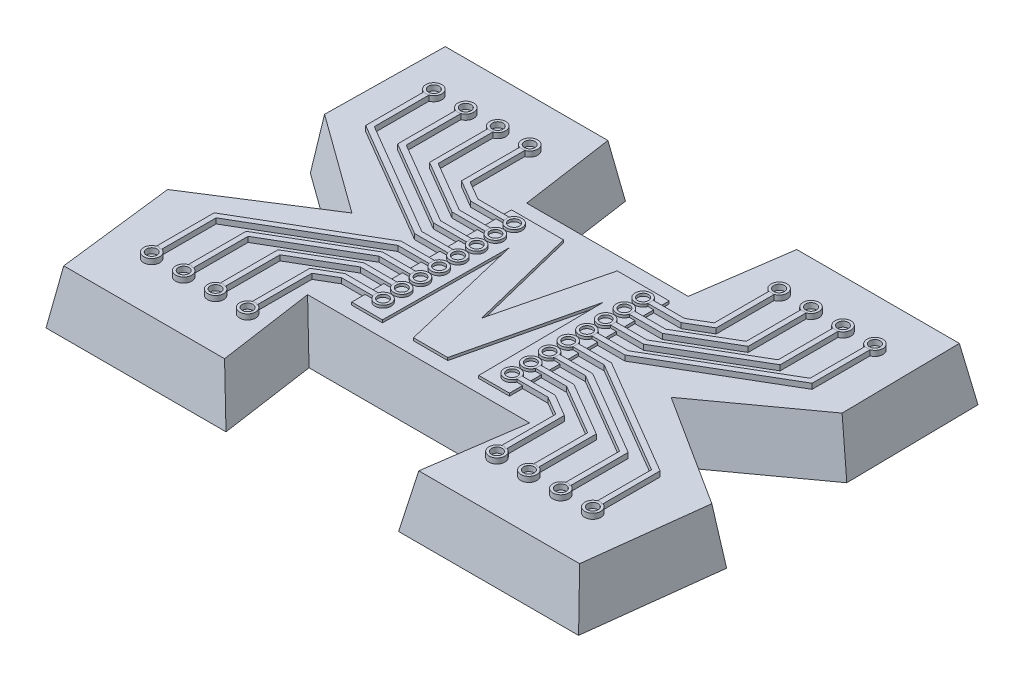
SolidWorks part; units mm, degrees
ref_plane "Спереди" through (0, 0, 0) normal (0, 0, 1) x (1, 0, 0)
ref_plane "Сверху" through (0, 0, 0) normal (0, 1, 0) x (1, 0, 0)
ref_plane "Справа" through (0, 0, 0) normal (1, 0, 0) x (0, 0, -1)
sketch "Эскиз1" plane through (0, 0, 0) normal (0, 1, 0) x (1, 0, 0)
  line L0 (0, 0) -> (-5.9483, 49.6449)
  line L1 (-5.9483, 49.6449) -> (33.7998, 75)
  line L2 (33.7998, 75) -> (-0.7287, 100.0053)
  line L3 (-0.7287, 100.0053) -> (0, 150)
  line L4 (0, 150) -> (67.5996, 150)
  line L5 (67.5996, 150) -> (72.7258, 114.3707)
  line L6 (72.7258, 114.3707) -> (127.2742, 114.3707)
  line L7 (0, 0) -> (67.5996, 0)
  line L8 (67.5996, 0) -> (62.3599, 36.418)
  line L9 (62.3599, 36.418) -> (137.6401, 36.418)
  line L10 (100, 114.3707) -> (100, 36.418) construction
  line L11 (33.7998, 0) -> (33.7998, 150) construction
  line L12 (166.2002, 0) -> (166.2002, 150) construction
  line L13 (132.4004, 0) -> (137.6401, 36.418)
  line L14 (200, 0) -> (132.4004, 0)
  line L15 (132.4004, 150) -> (127.2742, 114.3707)
  line L16 (200, 150) -> (132.4004, 150)
  line L17 (200.7287, 100.0053) -> (200, 150)
  line L18 (166.2002, 75) -> (200.7287, 100.0053)
  line L19 (205.9483, 49.6449) -> (166.2002, 75)
  line L20 (200, 0) -> (205.9483, 49.6449)
  dimension "D1" = 100
  dimension "D3" = 150
  dimension "D4" = 50
extrude "X" add sketch "Эскиз1" along normal blind 20 draft 10
sketch "Эскиз6" plane through (0, 20, 0) normal (0, 1, 0) x (1, 0, 0)
  line L0 (70, 104.8152) -> (70, 44.8152)
  line L1 (99.6154, 63.8897) -> (99.6154, 44.8152) construction
  line L2 (70, 44.8152) -> (81.5385, 44.8152)
  line L3 (81.5385, 44.8152) -> (81.9231, 92.0507)
  line L4 (81.9231, 92.0507) -> (93.1851, 44.8152)
  line L5 (70, 123.5265) -> (124.007, 123.5265) construction
  line L6 (93.1851, 44.8152) -> (106.0457, 44.8152)
  line L7 (106.0457, 44.8152) -> (117.3077, 92.0507)
  line L8 (117.3077, 92.0507) -> (117.6923, 44.8152)
  line L9 (117.6923, 44.8152) -> (129.2308, 44.8152)
  line L10 (129.2308, 44.8152) -> (129.2308, 104.8152)
  line L11 (70, 123.5265) -> (70, 26.4735) construction
  line L12 (70, 26.4735) -> (124.007, 26.4735) construction
  line L13 (129.2308, 104.8152) -> (109.7115, 104.8152)
  line L14 (109.7115, 104.8152) -> (99.6154, 63.8897)
  line L15 (99.6154, 63.8897) -> (89.5192, 104.8152)
  line L16 (89.5192, 104.8152) -> (70, 104.8152)
  line L17 (124.007, 123.5265) -> (124.007, 26.4735) construction
  line L18 (100, 39.9446) -> (100, 110.8442) construction
  line L19 (58.2897, 39.9446) -> (141.7103, 39.9446) construction
  line L20 (130.3296, 110.8442) -> (69.6704, 110.8442) construction
  point P9 (70, 74.8152)
  dimension "D1" = 19.5192
  dimension "D2" = 60
  dimension "D3" = 12.8606
  dimension "D4" = 11.5385
  dimension "D5" = 47.2356
  dimension "D6" = 13.877
  dimension "D7" = 13.877
  dimension "D8" = 27.716
  dimension "D9" = 90.467
  dimension "D10" = 90.467
  dimension "D11" = 30
extrude "M" add sketch "Эскиз6" along normal blind 1 and the other way blind 7 separate body
sketch "Эскиз9" plane through (0, 21, 0) normal (0, 1, 0) x (1, 0, 0)
  line L0 (75.7692, 44.8152) -> (75.7692, 104.8152) construction
  line L1 (70, 44.8152) -> (81.5385, 44.8152) construction
  line L2 (89.5192, 104.8152) -> (70, 104.8152) construction
  line L3 (100, 110.8442) -> (100, 39.9446) construction
  line L5 (58.2897, 39.9446) -> (141.7103, 39.9446) construction
  line L6 (130.3296, 110.8442) -> (69.6704, 110.8442) construction
  circle A0 centre (75.7692, 50.8152) radius 3
  circle A1 centre (75.7692, 50.8152) radius 2
  circle A2 centre (75.7692, 57.8416) radius 3
  circle A3 centre (75.7692, 57.8416) radius 2
  circle A4 centre (75.7692, 64.868) radius 3
  circle A5 centre (75.7692, 64.868) radius 2
  circle A6 centre (75.7692, 71.8944) radius 3
  circle A7 centre (75.7692, 71.8944) radius 2
  circle A8 centre (75.7692, 78.9208) radius 3
  circle A9 centre (75.7692, 78.9208) radius 2
  circle A10 centre (75.7692, 85.9472) radius 3
  circle A11 centre (75.7692, 85.9472) radius 2
  circle A12 centre (75.7692, 92.9736) radius 3
  circle A13 centre (75.7692, 92.9736) radius 2
  circle A14 centre (75.7692, 100) radius 3
  circle A15 centre (75.7692, 100) radius 2
  circle A16 centre (124.2308, 100) radius 2
  circle A17 centre (124.2308, 100) radius 3
  circle A18 centre (124.2308, 92.9736) radius 2
  circle A19 centre (124.2308, 92.9736) radius 3
  circle A20 centre (124.2308, 85.9472) radius 2
  circle A21 centre (124.2308, 85.9472) radius 3
  circle A22 centre (124.2308, 78.9208) radius 2
  circle A23 centre (124.2308, 78.9208) radius 3
  circle A24 centre (124.2308, 71.8944) radius 2
  circle A25 centre (124.2308, 71.8944) radius 3
  circle A26 centre (124.2308, 64.868) radius 2
  circle A27 centre (124.2308, 64.868) radius 3
  circle A28 centre (124.2308, 57.8416) radius 2
  circle A29 centre (124.2308, 57.8416) radius 3
  circle A30 centre (124.2308, 50.8152) radius 2
  circle A31 centre (124.2308, 50.8152) radius 3
  dimension "D2" = 4
  dimension "D3" = 6
  dimension "D1" = 6
extrude "M holes" add sketch "Эскиз9" along normal blind 1 and the other way blind 3
sketch "Эскиз8" plane through (0, 20, 0) normal (0, 1, 0) x (1, 0, 0)
  line L0 (3.2132, 128.4735) -> (17.1736, 128.4735) construction
  line L1 (17.1736, 128.4735) -> (53.1736, 128.4735) construction
  line L2 (53.1736, 128.4735) -> (67.1339, 128.4735) construction
  line L4 (64.5442, 146.4735) -> (3.4755, 146.4735) construction
  line L5 (3.4755, 146.4735) -> (2.8242, 101.7865) construction
  line L6 (100, 110.8442) -> (100, 39.9446) construction
  line L8 (58.2897, 39.9446) -> (141.7103, 39.9446) construction
  line L9 (3.1292, 3.5265) -> (63.5294, 3.5265) construction
  line L10 (17.1736, 128.4735) -> (29.1736, 128.4735) construction
  line L11 (130.3296, 110.8442) -> (69.6704, 110.8442) construction
  line L12 (17.1736, 22.5265) -> (29.1736, 22.5265) construction
  line L13 (53.1736, 22.5265) -> (196.753, 22.5265) construction
  line L14 (17.1736, 22.5265) -> (53.1736, 22.5265) construction
  line L15 (3.2132, 22.5265) -> (17.1736, 22.5265) construction
  line L16 (69.6704, 110.8442) -> (64.5442, 146.4735) construction
  circle A0 centre (17.1736, 128.4735) radius 3
  circle A1 centre (17.1736, 128.4735) radius 2
  circle A2 centre (29.1736, 128.4735) radius 2
  circle A3 centre (29.1736, 128.4735) radius 3
  circle A4 centre (41.1736, 128.4735) radius 2
  circle A5 centre (41.1736, 128.4735) radius 3
  circle A6 centre (53.1736, 128.4735) radius 2
  circle A7 centre (53.1736, 128.4735) radius 3
  circle A8 centre (182.8264, 22.5265) radius 3
  circle A9 centre (182.8264, 22.5265) radius 2
  circle A10 centre (170.8264, 22.5265) radius 2
  circle A11 centre (170.8264, 22.5265) radius 3
  circle A12 centre (158.8264, 22.5265) radius 2
  circle A13 centre (158.8264, 22.5265) radius 3
  circle A14 centre (146.8264, 22.5265) radius 2
  circle A15 centre (146.8264, 22.5265) radius 3
  circle A16 centre (53.1736, 22.5265) radius 3
  circle A17 centre (53.1736, 22.5265) radius 2
  circle A18 centre (41.1736, 22.5265) radius 3
  circle A19 centre (41.1736, 22.5265) radius 2
  circle A20 centre (29.1736, 22.5265) radius 3
  circle A21 centre (29.1736, 22.5265) radius 2
  circle A22 centre (17.1736, 22.5265) radius 2
  circle A23 centre (17.1736, 22.5265) radius 3
  circle A24 centre (146.8264, 128.4735) radius 3
  circle A25 centre (146.8264, 128.4735) radius 2
  circle A26 centre (158.8264, 128.4735) radius 3
  circle A27 centre (158.8264, 128.4735) radius 2
  circle A28 centre (170.8264, 128.4735) radius 3
  circle A29 centre (170.8264, 128.4735) radius 2
  circle A30 centre (182.8264, 128.4735) radius 2
  circle A31 centre (182.8264, 128.4735) radius 3
  circle A32 centre (13.3686, 14.8628) radius 2 [skipped]
  circle A33 centre (13.3686, 14.8628) radius 3 [skipped]
  circle A34 centre (25.3686, 14.8628) radius 2 [skipped]
  circle A35 centre (25.3686, 14.8628) radius 3 [skipped]
  circle A36 centre (37.3686, 14.8628) radius 2 [skipped]
  circle A37 centre (37.3686, 14.8628) radius 3 [skipped]
  circle A38 centre (49.3686, 14.8628) radius 2 [skipped]
  circle A39 centre (49.3686, 14.8628) radius 3 [skipped]
  dimension "D3" = 6
  dimension "D4" = 4
  dimension "D1" = 18
  dimension "D2" = 36
  dimension "D5" = 19
extrude "holes" add sketch "Эскиз8" along normal blind 2 and the other way blind 4 separate body
sketch "Эскиз10" plane through (0, 20, 0) normal (0, 1, 0) x (1, 0, 0)
  line L0 (17.1736, 128.4735) -> (17.1736, 104.4955) construction
  line L1 (17.1736, 104.4955) -> (60.8512, 78.9208) construction
  line L2 (60.8512, 78.9208) -> (75.7692, 78.9208) construction
  line L3 (29.1736, 128.4735) -> (29.1736, 104.4955) construction
  line L4 (29.1736, 104.4955) -> (60.8512, 85.9472) construction
  line L5 (60.8512, 85.9472) -> (75.7692, 85.9472) construction
  line L6 (75.7692, 92.9736) -> (60.8512, 92.9736) construction
  line L7 (60.8512, 92.9736) -> (41.1736, 104.4955) construction
  line L8 (41.1736, 104.4955) -> (41.1736, 128.4735) construction
  line L9 (53.1736, 128.4735) -> (53.1736, 104.4955) construction
  line L10 (53.1736, 104.4955) -> (60.8512, 100) construction
  line L11 (60.8512, 100) -> (75.7692, 100) construction
  line L12 (72.9408, 79.9208) -> (72.9408, 77.9208)
  line L13 (72.9408, 84.9472) -> (72.9408, 86.9472)
  line L14 (72.9408, 91.9736) -> (72.9408, 93.9736)
  line L15 (72.9408, 99) -> (72.9408, 101)
  line L17 (28.1736, 125.645) -> (30.1736, 125.645)
  line L18 (40.1736, 125.645) -> (42.1736, 125.645)
  line L19 (54.1736, 125.645) -> (52.1736, 125.645)
  line L20 (18.1736, 105.1174) -> (61.2054, 79.9208)
  line L21 (30.1736, 105.1161) -> (61.2032, 86.9472)
  line L22 (60.4969, 77.9208) -> (16.1736, 103.8736)
  line L23 (18.1736, 125.645) -> (18.1736, 105.1174)
  line L24 (61.2054, 79.9208) -> (72.9408, 79.9208)
  line L25 (72.9408, 77.9208) -> (60.4969, 77.9208)
  line L26 (16.1736, 125.645) -> (16.1736, 103.8736)
  line L27 (30.1736, 105.1161) -> (30.1736, 125.645)
  line L28 (60.4992, 84.9472) -> (28.1736, 103.8749)
  line L29 (28.1736, 125.645) -> (28.1736, 103.8749)
  line L30 (72.9408, 86.9472) -> (61.2032, 86.9472)
  line L31 (72.9408, 84.9472) -> (60.4992, 84.9472)
  line L32 (42.1736, 105.1198) -> (61.2095, 93.9736)
  line L33 (60.4928, 91.9736) -> (40.1736, 103.8712)
  line L34 (42.1736, 125.645) -> (42.1736, 105.1198)
  line L35 (40.1736, 125.645) -> (40.1736, 103.8712)
  line L36 (61.2095, 93.9736) -> (72.9408, 93.9736)
  line L37 (72.9408, 91.9736) -> (60.4928, 91.9736)
  line L38 (54.1736, 105.1147) -> (61.2008, 101)
  line L39 (60.5015, 99) -> (52.1736, 103.8763)
  line L40 (52.1736, 103.8763) -> (52.1736, 125.645)
  line L41 (54.1736, 125.645) -> (54.1736, 105.1147)
  line L42 (61.2008, 101) -> (72.9408, 101)
  line L43 (72.9408, 99) -> (60.5015, 99)
  line L44 (16.1736, 103.8736) -> (18.1736, 105.1174) construction
  line L45 (28.1736, 103.8749) -> (30.1736, 105.1161) construction
  line L46 (40.1736, 103.8712) -> (42.1736, 105.1198) construction
  line L47 (52.1736, 103.8763) -> (54.1736, 105.1147) construction
  line L48 (60.5015, 99) -> (61.2008, 101) construction
  line L49 (60.4928, 91.9736) -> (61.2095, 93.9736) construction
  line L50 (60.4992, 84.9472) -> (61.2032, 86.9472) construction
  line L51 (60.4969, 77.9208) -> (61.2054, 79.9208) construction
  line L52 (100, 110.8442) -> (100, 39.9446) construction
  line L53 (130.3296, 110.8442) -> (69.6704, 110.8442) construction
  line L54 (58.2897, 39.9446) -> (141.7103, 39.9446) construction
  line L55 (75.7692, 78.9208) -> (75.7692, 71.8944) construction
  line L56 (75.7692, 75.4076) -> (100, 75.3944) construction
  line L57 (139.5031, 77.9208) -> (138.7946, 79.9208) construction
  line L58 (139.5008, 84.9472) -> (138.7968, 86.9472) construction
  line L59 (139.5072, 91.9736) -> (138.7905, 93.9736) construction
  line L60 (139.4985, 99) -> (138.7992, 101) construction
  line L61 (147.8264, 103.8763) -> (145.8264, 105.1147) construction
  line L62 (159.8264, 103.8712) -> (157.8264, 105.1198) construction
  line L63 (171.8264, 103.8749) -> (169.8264, 105.1161) construction
  line L64 (183.8264, 103.8736) -> (181.8264, 105.1174) construction
  line L65 (146.8264, 104.4955) -> (139.1488, 100) construction
  line L66 (146.8264, 128.4735) -> (146.8264, 104.4955) construction
  line L67 (158.8264, 104.4955) -> (158.8264, 128.4735) construction
  line L68 (139.1488, 92.9736) -> (158.8264, 104.4955) construction
  line L69 (170.8264, 104.4955) -> (139.1488, 85.9472) construction
  line L70 (170.8264, 128.4735) -> (170.8264, 104.4955) construction
  line L71 (182.8264, 104.4955) -> (139.1488, 78.9208) construction
  line L72 (182.8264, 128.4735) -> (182.8264, 104.4955) construction
  line L73 (127.0592, 99) -> (139.4985, 99)
  line L74 (138.7992, 101) -> (127.0592, 101)
  line L75 (145.8264, 125.645) -> (145.8264, 105.1147)
  line L76 (147.8264, 103.8763) -> (147.8264, 125.645)
  line L77 (139.4985, 99) -> (147.8264, 103.8763)
  line L78 (145.8264, 105.1147) -> (138.7992, 101)
  line L79 (127.0592, 91.9736) -> (139.5072, 91.9736)
  line L80 (138.7905, 93.9736) -> (127.0592, 93.9736)
  line L81 (159.8264, 125.645) -> (159.8264, 103.8712)
  line L82 (157.8264, 125.645) -> (157.8264, 105.1198)
  line L83 (139.5072, 91.9736) -> (159.8264, 103.8712)
  line L84 (157.8264, 105.1198) -> (138.7905, 93.9736)
  line L85 (127.0592, 84.9472) -> (139.5008, 84.9472)
  line L86 (127.0592, 86.9472) -> (138.7968, 86.9472)
  line L87 (171.8264, 125.645) -> (171.8264, 103.8749)
  line L88 (139.5008, 84.9472) -> (171.8264, 103.8749)
  line L89 (169.8264, 105.1161) -> (169.8264, 125.645)
  line L90 (183.8264, 125.645) -> (183.8264, 103.8736)
  line L91 (127.0592, 77.9208) -> (139.5031, 77.9208)
  line L92 (138.7946, 79.9208) -> (127.0592, 79.9208)
  line L93 (181.8264, 125.645) -> (181.8264, 105.1174)
  line L94 (139.5031, 77.9208) -> (183.8264, 103.8736)
  line L95 (169.8264, 105.1161) -> (138.7968, 86.9472)
  line L96 (181.8264, 105.1174) -> (138.7946, 79.9208)
  line L97 (145.8264, 125.645) -> (147.8264, 125.645)
  line L98 (159.8264, 125.645) -> (157.8264, 125.645)
  line L99 (171.8264, 125.645) -> (169.8264, 125.645)
  line L100 (183.8264, 125.645) -> (181.8264, 125.645)
  line L101 (127.0592, 99) -> (127.0592, 101)
  line L102 (127.0592, 91.9736) -> (127.0592, 93.9736)
  line L103 (127.0592, 84.9472) -> (127.0592, 86.9472)
  line L104 (127.0592, 79.9208) -> (127.0592, 77.9208)
  line L105 (182.7685, 22.225) -> (182.7947, 46.203) construction
  line L106 (182.7947, 46.203) -> (139.1449, 71.8253) construction
  line L107 (170.7685, 22.2381) -> (170.7947, 46.2161) construction
  line L108 (170.7947, 46.2161) -> (139.1373, 64.7989) construction
  line L109 (139.1296, 57.7725) -> (158.7947, 46.2291) construction
  line L110 (158.7947, 46.2291) -> (158.7686, 22.2512) construction
  line L111 (146.7686, 22.2643) -> (146.7947, 46.2422) construction
  line L112 (146.7947, 46.2422) -> (139.122, 50.7461) construction
  line L113 (183.7954, 46.8238) -> (181.794, 45.5822) construction
  line L114 (171.7954, 46.8356) -> (169.794, 45.5966) construction
  line L115 (159.7954, 46.8523) -> (157.794, 45.6059) construction
  line L116 (147.7954, 46.8603) -> (145.794, 45.6241) construction
  line L117 (139.4727, 51.7457) -> (138.7712, 49.7465) construction
  line L118 (139.4891, 58.7721) -> (138.7702, 56.7729) construction
  line L119 (139.4904, 65.7985) -> (138.7842, 63.7993) construction
  line L120 (139.5003, 72.8249) -> (138.7896, 70.8257) construction
  line L121 (60.4942, 72.911) -> (61.2005, 70.9103) construction
  line L122 (60.4888, 65.8846) -> (61.1906, 63.8839) construction
  line L123 (60.4748, 58.8582) -> (61.1893, 56.8575) construction
  line L124 (60.4758, 51.8318) -> (61.1729, 49.8311) construction
  line L125 (52.1425, 46.9646) -> (54.1412, 45.724) construction
  line L126 (40.1425, 46.9828) -> (42.1412, 45.732) construction
  line L127 (28.1426, 46.9921) -> (30.1412, 45.7488) construction
  line L128 (16.1426, 47.0065) -> (18.1412, 45.7606) construction
  line L129 (60.8244, 50.8314) -> (75.7424, 50.8152) construction
  line L130 (53.1419, 46.3443) -> (60.8244, 50.8314) construction
  line L131 (53.1157, 22.3664) -> (53.1419, 46.3443) construction
  line L132 (41.1419, 46.3574) -> (41.1157, 22.3794) construction
  line L133 (60.832, 57.8578) -> (41.1419, 46.3574) construction
  line L134 (75.7501, 57.8416) -> (60.832, 57.8578) construction
  line L135 (60.8397, 64.8842) -> (75.7577, 64.868) construction
  line L136 (29.1419, 46.3705) -> (60.8397, 64.8842) construction
  line L137 (29.1157, 22.3925) -> (29.1419, 46.3705) construction
  line L138 (60.8474, 71.9106) -> (75.7654, 71.8944) construction
  line L139 (17.1419, 46.3835) -> (60.8474, 71.9106) construction
  line L140 (17.1157, 22.4056) -> (17.1419, 46.3835) construction
  line L141 (127.0542, 70.8385) -> (127.0564, 72.8385)
  line L142 (127.0488, 65.8121) -> (127.0466, 63.8121)
  line L143 (127.0411, 58.7857) -> (127.0389, 56.7857)
  line L144 (127.0334, 51.7593) -> (127.0313, 49.7593)
  line L145 (183.7716, 25.0524) -> (181.7716, 25.0546)
  line L146 (171.7716, 25.0655) -> (169.7716, 25.0676)
  line L147 (159.7716, 25.0785) -> (157.7716, 25.0807)
  line L148 (145.7716, 25.0938) -> (147.7716, 25.0916)
  line L149 (181.794, 45.5822) -> (138.7896, 70.8257)
  line L150 (169.794, 45.5966) -> (138.7842, 63.7993)
  line L151 (139.5003, 72.8249) -> (183.7954, 46.8238)
  line L152 (181.7716, 25.0546) -> (181.794, 45.5822)
  line L153 (138.7896, 70.8257) -> (127.0542, 70.8385)
  line L154 (127.0564, 72.8385) -> (139.5003, 72.8249)
  line L155 (183.7716, 25.0524) -> (183.7954, 46.8238)
  line L156 (169.794, 45.5966) -> (169.7716, 25.0676)
  line L157 (139.4904, 65.7985) -> (171.7954, 46.8356)
  line L158 (171.7716, 25.0655) -> (171.7954, 46.8356)
  line L159 (127.0466, 63.8121) -> (138.7842, 63.7993)
  line L160 (127.0488, 65.8121) -> (139.4904, 65.7985)
  line L161 (157.794, 45.6059) -> (138.7702, 56.7729)
  line L162 (139.4891, 58.7721) -> (159.7954, 46.8523)
  line L163 (157.7716, 25.0807) -> (157.794, 45.6059)
  line L164 (159.7716, 25.0785) -> (159.7954, 46.8523)
  line L165 (138.7702, 56.7729) -> (127.0389, 56.7857)
  line L166 (127.0411, 58.7857) -> (139.4891, 58.7721)
  line L167 (145.794, 45.6241) -> (138.7712, 49.7465)
  line L168 (139.4727, 51.7457) -> (147.7954, 46.8603)
  line L169 (147.7954, 46.8603) -> (147.7716, 25.0916)
  line L170 (145.7716, 25.0938) -> (145.794, 45.6241)
  line L171 (138.7712, 49.7465) -> (127.0313, 49.7593)
  line L172 (127.0334, 51.7593) -> (139.4727, 51.7457)
  line L173 (72.9151, 51.8183) -> (60.4758, 51.8318)
  line L174 (61.1729, 49.8311) -> (72.9129, 49.8183)
  line L175 (54.1188, 25.1937) -> (54.1412, 45.724)
  line L176 (52.1425, 46.9646) -> (52.1188, 25.1959)
  line L177 (60.4758, 51.8318) -> (52.1425, 46.9646)
  line L178 (54.1412, 45.724) -> (61.1729, 49.8311)
  line L179 (72.9227, 58.8447) -> (60.4748, 58.8582)
  line L180 (61.1893, 56.8575) -> (72.9206, 56.8447)
  line L181 (40.1188, 25.209) -> (40.1425, 46.9828)
  line L182 (42.1188, 25.2068) -> (42.1412, 45.732)
  line L183 (60.4748, 58.8582) -> (40.1425, 46.9828)
  line L184 (42.1412, 45.732) -> (61.1893, 56.8575)
  line L185 (72.9304, 65.8711) -> (60.4888, 65.8846)
  line L186 (72.9282, 63.8711) -> (61.1906, 63.8839)
  line L187 (28.1188, 25.222) -> (28.1426, 46.9921)
  line L188 (60.4888, 65.8846) -> (28.1426, 46.9921)
  line L189 (30.1412, 45.7488) -> (30.1188, 25.2199)
  line L190 (16.1188, 25.2351) -> (16.1426, 47.0065)
  line L191 (72.9381, 72.8975) -> (60.4942, 72.911)
  line L192 (61.2005, 70.9103) -> (72.9359, 70.8975)
  line L193 (18.1188, 25.2329) -> (18.1412, 45.7606)
  line L194 (60.4942, 72.911) -> (16.1426, 47.0065)
  line L195 (30.1412, 45.7488) -> (61.1906, 63.8839)
  line L196 (18.1412, 45.7606) -> (61.2005, 70.9103)
  line L197 (54.1188, 25.1937) -> (52.1188, 25.1959)
  line L198 (40.1188, 25.209) -> (42.1188, 25.2068)
  line L199 (28.1188, 25.222) -> (30.1188, 25.2199)
  line L200 (16.1188, 25.2351) -> (18.1188, 25.2329)
  line L201 (72.9151, 51.8183) -> (72.9129, 49.8183)
  line L202 (72.9227, 58.8447) -> (72.9206, 56.8447)
  line L203 (72.9304, 65.8711) -> (72.9282, 63.8711)
  line L204 (72.9359, 70.8975) -> (72.9381, 72.8975)
  arc A0 (16.1736, 125.645) -> (18.1736, 125.645) centre (17.1736, 128.4735) ccw
  circle A2 centre (17.1736, 128.4735) radius 3 construction
  circle A5 centre (17.1736, 128.4735) radius 2 construction
  circle A6 centre (75.7692, 78.9208) radius 3 construction
  circle A7 centre (75.7692, 78.9208) radius 3 construction
  circle A8 centre (75.7692, 85.9472) radius 3 construction
  circle A10 centre (75.7692, 92.9736) radius 3 construction
  circle A17 centre (75.7692, 100) radius 3 construction
  circle A18 centre (75.7692, 100) radius 3 construction
  circle A19 centre (75.7692, 100) radius 2 construction
  circle A20 centre (75.7692, 92.9736) radius 2 construction
  circle A21 centre (75.7692, 85.9472) radius 2 construction
  circle A22 centre (75.7692, 78.9208) radius 2 construction
  circle A23 centre (29.1736, 128.4735) radius 3 construction
  circle A24 centre (41.1736, 128.4735) radius 3 construction
  circle A25 centre (53.1736, 128.4735) radius 3 construction
  dimension "D1" = 2
  dimension "D2" = 2
extrude "routes" add sketch "Эскиз10" along normal blind 2 separate body
equation "\"D1@Эскиз10\" = \"d\""
equation "\"D2@Эскиз10\" = \"d\""
